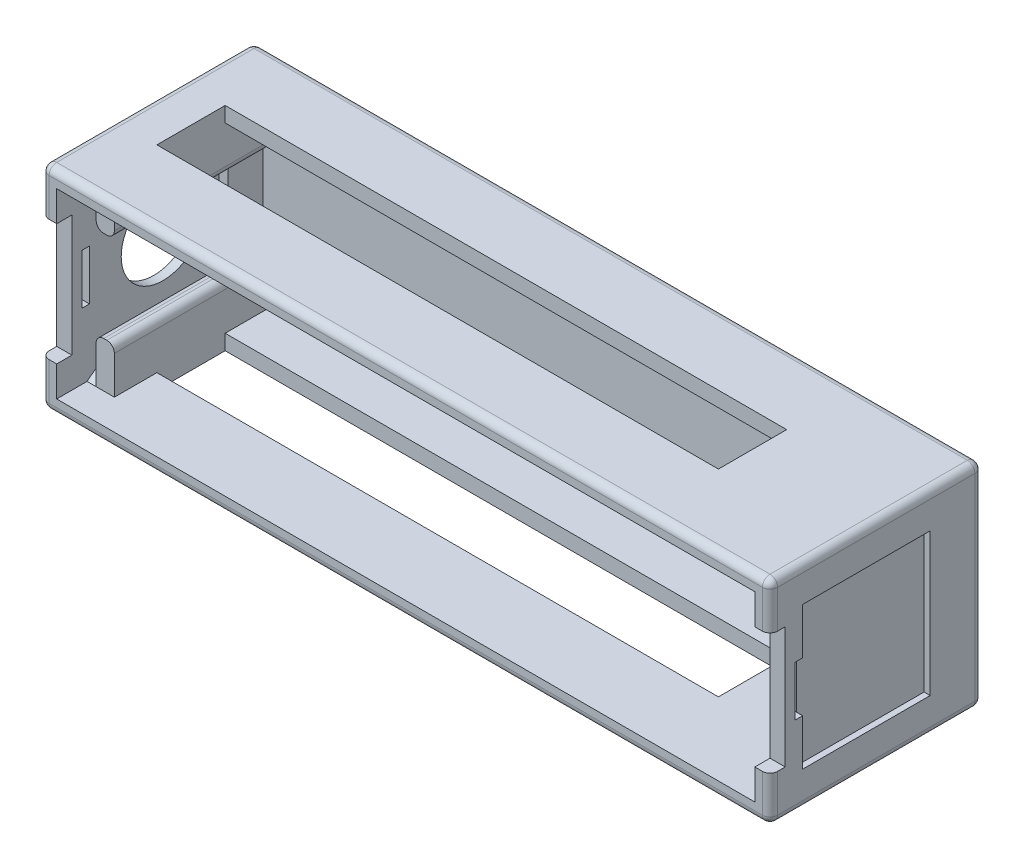
SolidWorks part; units mm, degrees
ref_plane "Спереди" through (0, 0, 0) normal (0, 0, 1) x (1, 0, 0)
ref_plane "Сверху" through (0, 0, 0) normal (0, 1, 0) x (1, 0, 0)
ref_plane "Справа" through (0, 0, 0) normal (1, 0, 0) x (0, 0, -1)
sketch "Sketch3" plane through (0, 0, 0) normal (0, 0, 1) x (1, 0, 0)
  line L1 (-24, -7) -> (24, -7)
  line L2 (-24, -7) -> (-24, 7)
  line L3 (-24, 7) -> (24, 7)
  line L4 (24, -7) -> (24, 7)
  line L5 (-24, -7) -> (24, 7) construction
  line L6 (-24, 7) -> (24, -7) construction
  point P0 (0, 0)
  dimension "D1" = 48
  dimension "D2" = 14
extrude "Boss-Extrude2" add sketch "Sketch3" along normal blind 14
sketch "Sketch4" plane through (0, 0, 14) normal (0, 0, 1) x (1, 0, 0)
  line L0 (24, -7) -> (24, 7) construction
  line L1 (-23, -6) -> (23, -6)
  line L2 (-23, -6) -> (-23, 6)
  line L3 (-23, 6) -> (23, 6)
  line L4 (23, -6) -> (23, 6)
  line L5 (-23, -6) -> (23, 6) construction
  line L6 (-23, 6) -> (23, -6) construction
  line L7 (-24, -7) -> (24, -7) construction
  point P0 (0, 0)
  dimension "D1" = 1
  dimension "D2" = 1
  dimension "D3" = 12
  dimension "D4" = 46
extrude "Cut-Extrude1" cut sketch "Sketch4" against normal offset from surface (13 mm away) 1 up to face at (0, 0, 0)
fillet "Fillet1" radius 0.5 12 edges at (24, 0, 14) (24, 0, 0) (-24, 0, 14) (-24, 0, 0) (-24, -7, 7) (0, -7, 14) (24, -7, 7) (0, -7, 0) (24, 7, 7) (0, 7, 14) (-24, 7, 7) (0, 7, 0)
sketch "Sketch6" plane through (0, -7, 0) normal (0, -1, 0) x (1, 0, 0)
  line L0 (-23.5, 4.7) -> (23.5, 4.7) construction
  line L1 (-23.5, 13.5) -> (-23.5, 0.5) construction
  line L2 (23.5, 0.5) -> (23.5, 13.5) construction
  line L3 (-23.5, 0.5) -> (23.5, 0.5) construction
  line L4 (-23.5, 9.2) -> (23.5, 9.2) construction
  line L6 (-21.2, 4.7) -> (15.8, 4.7)
  line L7 (-21.2, 4.7) -> (-21.2, 9.2)
  line L8 (-21.2, 9.2) -> (15.8, 9.2)
  line L9 (15.8, 4.7) -> (15.8, 9.2)
  dimension "D1" = 4.2
  dimension "D2" = 4.5
  dimension "D3" = 37
  dimension "D4" = 7.7
extrude "Cut-Extrude2" cut sketch "Sketch6" against normal through all both and the other way through all
ref_plane "Plane2" through (0, 0, 14) normal (0, 0, 1) x (1, 0, 0)
sketch "Sketch14" plane through (0, 0, 14) normal (0, 0, 1) x (1, 0, 0)
  line L0 (23.5, 6.5) -> (-23.5, 6.5) construction
  line L1 (-10, 6) -> (10, 6)
  line L2 (-10, 6) -> (-10, 7)
  line L3 (-10, 7) -> (10, 7)
  line L4 (10, 6) -> (10, 7)
  line L5 (-10, 6) -> (10, 7) construction
  line L6 (-10, 7) -> (10, 6) construction
  point P0 (0, 6.5)
  dimension "D1" = 1
  dimension "D2" = 20
extrude "Cut-Extrude8" [suppressed] cut sketch "Sketch14" against normal blind 1
ref_plane "Plane3" through (0, 0, 0) normal (0, -1, 0) x (-1, 0, 0)
mirror "Mirror1" [suppressed] about plane through (0, 0, 0) normal (0, -1, 0)
ref_plane "Plane4" through (0, 0, 0) normal (-1, 0, 0) x (0, 0, 1)
sketch "Sketch15" plane through (0, 0, 14) normal (0, 0, 1) x (1, 0, 0)
  line L0 (23.5, -6.5) -> (23.5, 6.5) construction
  line L1 (23, -6) -> (23, 6) construction
  line L2 (24, -4) -> (23, -4)
  line L3 (24, -4) -> (24, 4)
  line L4 (24, 4) -> (23, 4)
  line L5 (23, -4) -> (23, 4)
  line L6 (24, -4) -> (23, 4) construction
  line L7 (24, 4) -> (23, -4) construction
  line L8 (24, 6.5) -> (24, -6.5) construction
  point P2 (23.5, 0)
  dimension "D1" = 8
extrude "Cut-Extrude9" cut sketch "Sketch15" against normal blind 1
mirror "Mirror3" about plane through (0, 0, 0) normal (-1, 0, 0) of "Cut-Extrude9"
sketch "Sketch17" plane through (0, 0, 1) normal (0, 0, 1) x (1, 0, 0)
  line L0 (23, 0) -> (-23, 0) construction
  line L1 (20, 4.675) -> (19.45, 4.675)
  line L2 (21.5, 3.175) -> (21.5, -3.175)
  line L3 (20, -4.675) -> (19.45, -4.675)
  line L4 (17.95, 3.175) -> (17.95, -3.175)
  line L5 (21.5, 4.675) -> (17.95, -4.675) construction
  line L6 (21.5, -4.675) -> (17.95, 4.675) construction
  line L7 (23, -6) -> (23, 6) construction
  line L8 (-23, 6) -> (-23, -6) construction
  arc A0 (21.5, -3.175) -> (20, -4.675) centre (20, -3.175) cw
  arc A1 (19.45, -4.675) -> (17.95, -3.175) centre (19.45, -3.175) cw
  arc A2 (19.45, 4.675) -> (17.95, 3.175) centre (19.45, 3.175) ccw
  arc A3 (20, 4.675) -> (21.5, 3.175) centre (20, 3.175) cw
  point P0 (19.725, 0)
  dimension "D4" = 1.5
  dimension "D1" = 9.35
  dimension "D2" = 3.55
  dimension "D3" = 1.5
extrude "Cut-Extrude10" cut sketch "Sketch17" against normal through all
sketch "Sketch20" plane through (0, -6, 0) normal (0, 1, 0) x (1, 0, 0)
  line L0 (-23, -1) -> (23, -1) construction
  line L1 (-21.2, -1) -> (-22.4, -1)
  line L2 (-21.2, -1) -> (-21.2, -12)
  line L3 (-21.2, -12) -> (-22.4, -12)
  line L4 (-22.4, -1) -> (-22.4, -12)
  line L5 (-23, -14) -> (23, -14) construction
  line L7 (-23, -1) -> (-23, -14) construction
  line L8 (-21.2, -9.2) -> (-21.2, -4.7) construction
  dimension "D1" = 2
  dimension "D3" = 0.6
  dimension "D4" = 1.2
extrude "Boss-Extrude3" add sketch "Sketch20" along normal blind 3
fillet "Fillet2" radius 0.5 2 edges at (-22.4, -3, 6.5) (-21.2, -3, 6.5)
mirror "Mirror4" about plane through (0, 0, 0) normal (0, -1, 0) of "Boss-Extrude3", "Fillet2"
sketch "Sketch24" plane through (-24, 0, 0) normal (-1, 0, 0) x (0, 0, 1)
  line L0 (13.5, 6.5) -> (0.5, -6.5) construction
  circle A0 centre (7, 0) radius 2.75
  dimension "D1" = 5.5
extrude "Cut-Extrude14" cut sketch "Sketch24" against normal up to surface (1 mm away) up to face at (-23, 0, 10.5)
sketch "Sketch25" plane through (0, 0, 1) normal (0, 0, 1) x (1, 0, 0)
  line L0 (-22.4, -3.5) -> (-22.4, -6) construction
  line L1 (-22.4, 6) -> (-22.4, -6)
  line L3 (-22.4, 6) -> (-23, 6) construction
  line L4 (-22.4, 6) -> (-23, 6)
  line L5 (-23, 6) -> (-23, -6) construction
  line L6 (-23, 6) -> (-23, -6)
  line L7 (-23, -6) -> (-22.4, -6) construction
  line L8 (-23, -6) -> (-22.4, -6)
extrude "Boss-Extrude4" add sketch "Sketch25" along normal blind 2.3
sketch "Sketch28" plane through (24, 0, 0) normal (1, 0, 0) x (0, 0, -1)
  line L0 (-13, 0) -> (-0.5, 0) construction
  line L1 (-13, -4) -> (-13, 4) construction
  line L2 (-0.5, -6.5) -> (-0.5, 6.5) construction
  line L4 (-3.45, -4.7) -> (-11.85, -4.7)
  line L5 (-3.45, -4.7) -> (-3.45, 4.7)
  line L6 (-3.45, 4.7) -> (-11.85, 4.7)
  line L7 (-11.85, -4.7) -> (-11.85, 4.7)
  point P6 (-6.75, 0)
  dimension "D1" = 8.4
  dimension "D2" = 9.4
  dimension "D3" = 3.3
  dimension "D4" = 4.7
  dimension "D5" = 4.7
extrude "Cut-Extrude15" cut sketch "Sketch28" against normal blind 0.4
sketch "Sketch30" plane through (0, 0, 1) normal (0, 0, 1) x (1, 0, 0)
  line L1 (23, -6) -> (22.3, -6)
  line L2 (23, -6) -> (23, 6)
  line L3 (23, 6) -> (22.3, 6)
  line L4 (22.3, -6) -> (22.3, 6)
  dimension "D1" = 0.7
extrude "Boss-Extrude6" add sketch "Sketch30" along normal up to surface (12 mm away) up to face at (23.5, 0, 13)
sketch "Sketch35" plane through (0, 0, 1) normal (0, 0, 1) x (1, 0, 0)
  line L0 (-21.2, -6) -> (22.3, -6) construction
  line L1 (22.3, 6) -> (-21.2, 6) construction
  line L2 (22.3, 6) -> (22.3, -6) construction
  line L3 (20.8, -6) -> (22.3, -6)
  line L4 (22.3, 6) -> (20.8, 6)
  line L5 (22.3, 6) -> (22.3, -6)
  line L6 (20.8, 6) -> (20.8, -6)
  dimension "D1" = 1.5
extrude "Cut-Extrude19" cut sketch "Sketch35" against normal blind 0.6
fillet "Fillet3" radius 0.2 1 edges at (20.8, 4.4439, 0.7)
fillet "Fillet4" radius 0.2 1 edges at (20.8, -4.4439, 0.7)
sketch "Sketch36" plane through (0, 0, 13) normal (0, 0, 1) x (1, 0, 0)
  line L0 (22.3, 6) -> (22.3, -6) construction
  line L1 (22.3, 6) -> (22.3, -6)
  line L2 (23, 6) -> (22.3, 6) construction
  line L3 (23, 6) -> (22.3, 6)
  line L4 (22.3, -6) -> (23, -6) construction
  line L5 (22.3, -6) -> (23, -6)
  line L6 (23, 6) -> (23, -6)
  dimension "D1" = 0.7
extrude "Cut-Extrude20" cut sketch "Sketch36" against normal up to surface (12.6 mm away) up to face at (21.2395, 0, 0.4)
sketch "Sketch38" plane through (24, 0, 0) normal (1, 0, 0) x (0, 0, -1)
  line L0 (-13, -4) -> (-13, 4) construction
  line L2 (-13, -4) -> (-13, 4) construction
  line L3 (-11.85, 4.7) -> (-11.85, -4.7) construction
  line L4 (-12.1, -1.65) -> (-12.1, 1.65) construction
  line L5 (-12.35, -1.65) -> (-11.85, -1.65)
  line L6 (-12.35, -1.65) -> (-12.35, 1.65)
  line L7 (-12.35, 1.65) -> (-11.85, 1.65)
  line L8 (-11.85, -1.65) -> (-11.85, 1.65)
  line L9 (-12.1, 0) -> (-11.85, 0) construction
  point P10 (-11.85, 0)
  point P11 (-12.1, 0)
  point P14 (-11.85, 0)
  dimension "D1" = 1.15
  dimension "D2" = 3.3
  dimension "D3" = 0.5
extrude "Cut-Extrude22" cut sketch "Sketch38" against normal up to surface (1 mm away) up to face at (23, 0, 10.35)
sketch "Sketch39" plane through (0, 0, 3.3) normal (0, 0, 1) x (1, 0, 0)
  line L0 (-23, 0) -> (-22.4, 0) construction
  line L1 (-23, 6) -> (-23, -6) construction
  line L2 (-22.4, -3.5) -> (-22.4, 3.5) construction
  line L3 (-22.7, -4.75) -> (-22.7, 4.75) construction
  line L5 (-23, 6) -> (-23, 4.75)
  line L6 (-22.4, 6) -> (-23, 6) construction
  line L9 (-22.4, 6) -> (-23, 6)
  line L10 (-22.4, 3.5) -> (-22.4, 6) construction
  line L11 (-22.4, 4.75) -> (-22.4, 6)
  line L12 (-23, 4.75) -> (-22.4, 4.75)
  line L13 (-23, -6) -> (-23, -4.75)
  line L14 (-22.4, -6) -> (-23, -6)
  line L15 (-22.4, -4.75) -> (-22.4, -6)
  line L16 (-23, -4.75) -> (-22.4, -4.75)
  point P8 (-22.7, 0)
  point P9 (-22.7, 0)
  dimension "D1" = 9.5
extrude "Boss-Extrude7" add sketch "Sketch39" along normal up to surface (8.7 mm away) up to face at (-21.8, -4.1321, 12)
fillet "Fillet5" radius 5 2 edges at (-22.7, 4.75, 12) (-22.7, -4.75, 12)
mirror "Mirror5" about plane through (0, 0, 0) normal (-1, 0, 0) of "Cut-Extrude22", "Cut-Extrude15"
